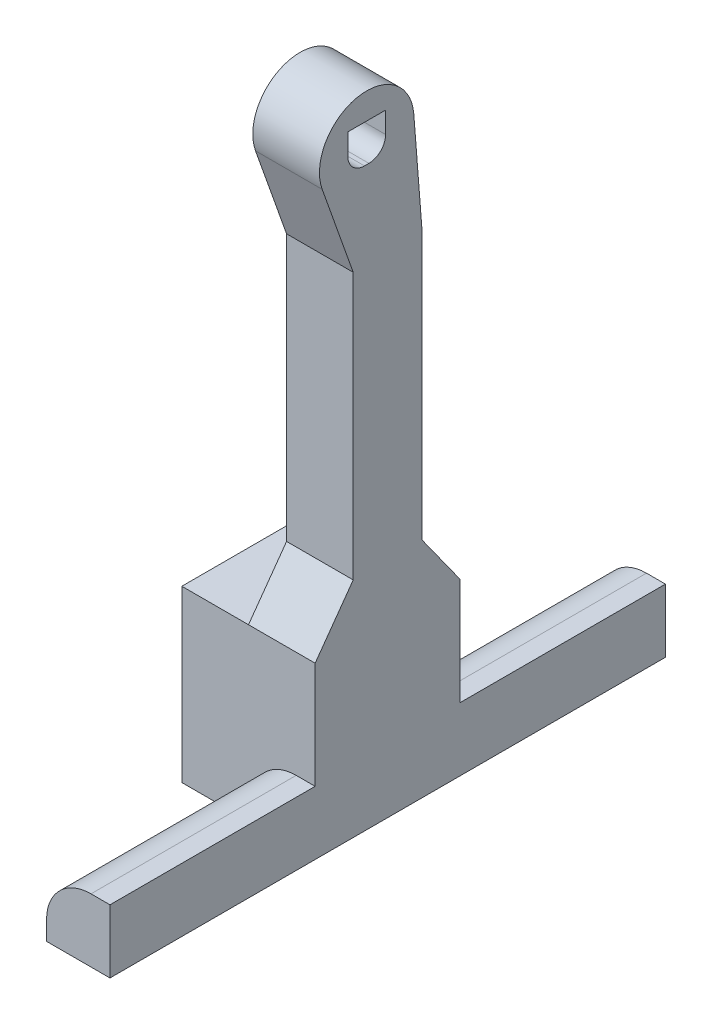
SolidWorks part; units mm, degrees
ref_plane "Front Plane" through (0, 0, 0) normal (0, 0, 1) x (1, 0, 0)
ref_plane "Top Plane" through (0, 0, 0) normal (0, 1, 0) x (1, 0, 0)
ref_plane "Right Plane" through (0, 0, 0) normal (1, 0, 0) x (0, 0, -1)
sketch "Sketch1" plane through (0, 0, 0) normal (1, 0, 0) x (0, 0, -1)
  line L0 (-3, 9.82) -> (-3, 0)
  line L1 (-3, 0) -> (-6.5301, 0)
  line L2 (-6.5301, 0) -> (-6.5301, 9.82)
  line L3 (-6.5301, 15.3053) -> (-3.1034, 20.0847)
  line L4 (-3.1034, 20.0847) -> (-3.1034, 44.065)
  line L5 (0, 0) -> (0, 50000) construction
  line L6 (3.1034, 20.0847) -> (3.1034, 44.065)
  line L7 (6.5301, 15.3053) -> (3.1034, 20.0847)
  line L8 (6.5301, 0) -> (6.5301, 9.82)
  line L9 (3, 0) -> (6.5301, 0)
  line L10 (3, 9.82) -> (3, 0)
  line L11 (-3, 9.82) -> (3, 9.82)
  line L12 (-2.0907, 52.0529) -> (-1.6907, 52.0529) construction
  line L13 (-2.0907, 53.3529) -> (-1.6907, 53.3529) construction
  line L14 (-3.3907, 55.0529) -> (-3.3907, 53.3529) construction
  line L15 (-0.3907, 53.3529) -> (-0.3907, 55.0529) construction
  line L16 (-0.3907, 55.0529) -> (-3.3907, 55.0529) construction
  line L17 (-3.3907, 55.0529) -> (-0.3907, 55.0529) construction
  line L18 (-2.0907, 52.0529) -> (-1.6907, 52.0529) construction
  line L19 (-3.3907, 55.0529) -> (-3.3907, 53.3529) construction
  line L20 (-0.3907, 53.3529) -> (-0.3907, 55.0529) construction
  line L21 (-0.3907, 55.0529) -> (-3.3907, 55.0529) construction
  line L22 (-3.3907, 55.0529) -> (-0.3907, 55.0529)
  line L23 (-3.1034, 44.065) -> (-5.8976, 51.9292)
  line L24 (3.1034, 44.065) -> (2.3486, 53.6855)
  line L25 (6.5301, 9.82) -> (6.5301, 15.3053)
  line L26 (-6.5301, 9.82) -> (-6.5301, 15.3053)
  line L27 (-6.5301, 9.82) -> (-3, 9.82)
  line L28 (3, 9.82) -> (6.5301, 9.82)
  line L29 (3, 0) -> (-3, 0)
  line L30 (6.5301, 15.3053) -> (-6.5301, 15.3053)
  line L31 (-0.1907, 55.2529) -> (-3.5907, 55.2529)
  line L32 (-3.5907, 55.2529) -> (-3.5907, 53.3529)
  line L33 (-2.0907, 51.8529) -> (-1.6907, 51.8529)
  line L34 (-0.1907, 53.3529) -> (-0.1907, 55.2529)
  line L35 (-25, 12.1535) -> (-25, -1.9655) construction
  line L36 (25, 12.1535) -> (25, -1.9655) construction
  arc A0 (-1.6907, 52.0529) -> (-0.3907, 53.3529) centre (-1.6907, 53.3529) ccw construction
  arc A1 (-3.3907, 53.3529) -> (-2.0907, 52.0529) centre (-2.0907, 53.3529) ccw construction
  arc A2 (-1.6907, 52.0529) -> (-0.3907, 53.3529) centre (-1.6907, 53.3529) ccw construction
  arc A3 (-3.3907, 53.3529) -> (-2.0907, 52.0529) centre (-2.0907, 53.3529) ccw construction
  arc A4 (-5.8976, 51.9292) -> (2.3486, 53.6855) centre (-1.8907, 53.3529) cw
  arc A5 (-3.5907, 53.3529) -> (-2.0907, 51.8529) centre (-2.0907, 53.3529) ccw
  arc A6 (-1.6907, 51.8529) -> (-0.1907, 53.3529) centre (-1.6907, 53.3529) ccw
  dimension "D3" = 0.2
  dimension "D1" = 6
  dimension "D2" = 9.82
  dimension "D4" = 25
extrude "Boss-Extrude2" add sketch "Sketch1" against normal blind 6 contours L28 L10 L9 L8 | L27 L2 L1 L0 | L25 L30 L26 L27 L11 L28 region at (0, 12.5626, 0) region at (0, 4.91, 4.7651) region at (0, 4.91, -4.7651)
extrude "Boss-Extrude3" add sketch "Sketch1<4>" along normal blind 6 contours L29 L10 L11 L0 | L27 L2 L1 L0 | L28 L10 L9 L8 | L25 L30 L26 L27 L11 L28 | A4 L23 L4 L3 L30 L7 L6 L24 A3 L19 L21 L20 A2 L18 region at (0, 4.91, 0) region at (0, 12.5626, 0) region at (0, 4.91, 4.7651) region at (0, 4.91, -4.7651) region at (0, 35.3535, 0.3792)
sketch "Sketch1<4>" plane through (0, 0, 0) normal (1, 0, 0) x (0, 0, -1) same geometry as "Sketch1"
sketch "Sketch4" plane through (0, 0, 6.5301) normal (0, 0, 1) x (1, 0, 0)
  line L1 (6, 0) -> (0.2928, 0)
  line L2 (6, 0) -> (6, 5.7072)
  line L3 (6, 5.7072) -> (4.2928, 5.7072)
  line L4 (0.2928, 0) -> (0.2928, 1.7072)
  arc A0 (0.2928, 1.7072) -> (4.2928, 5.7072) centre (4.2928, 1.7072) cw
  dimension "D1" = 4
extrude "Boss-Extrude4" add sketch "Sketch4" along normal up to vertex (18.4699 mm away) and the other way up to vertex (31.5301 mm away) up to point (0, -1.9655, 25) other way up to point (0, -1.9655, -25)
